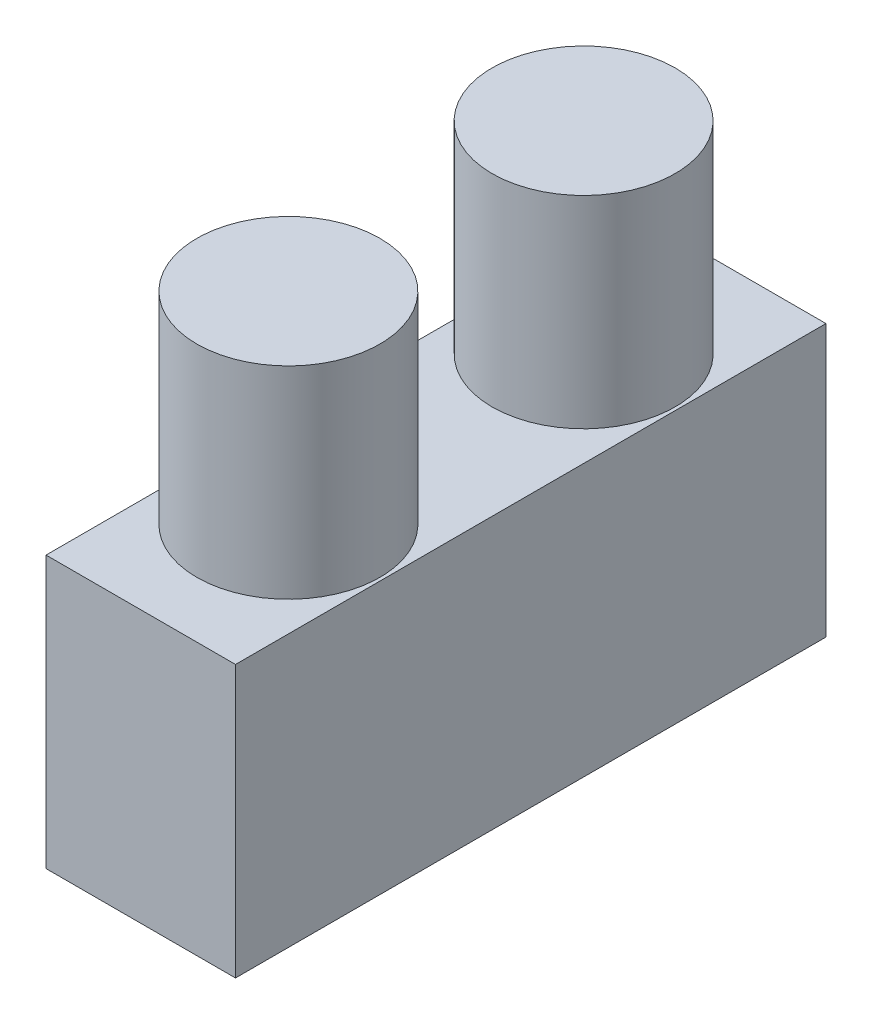
SolidWorks part; units mm, degrees
ref_plane "Front Plane" through (0, 0, 0) normal (0, 0, 1) x (1, 0, 0)
ref_plane "Top Plane" through (0, 0, 0) normal (0, 1, 0) x (1, 0, 0)
ref_plane "Right Plane" through (0, 0, 0) normal (1, 0, 0) x (0, 0, -1)
sketch "Sketch1" plane through (0, 0, 0) normal (0, 1, 0) x (1, 0, 0)
  line L1 (0, 0) -> (6, 0)
  line L2 (0, 0) -> (0, 18.7)
  line L3 (0, 18.7) -> (6, 18.7)
  line L4 (6, 0) -> (6, 18.7)
  dimension "D1" = 6
  dimension "D2" = 18.7
extrude "Boss-Extrude1" add sketch "Sketch1" along normal blind 8.6
sketch "Sketch2" plane through (0, 8.6, 0) normal (0, 1, 0) x (1, 0, 0)
  line L0 (3, 18.7) -> (3, 14.025) construction
  line L3 (6, 18.7) -> (0, 18.7) construction
  line L4 (3, 14.025) -> (3, 9.35) construction
  line L5 (3, 9.35) -> (3, 4.675) construction
  line L6 (3, 4.675) -> (3, 0) construction
  line L7 (0, 0) -> (6, 0) construction
  circle A0 centre (3, 14.025) radius 2.9
  circle A1 centre (3, 4.675) radius 2.9
  point P11 (0, 0)
  point P12 (0, 0)
  dimension "D2" = 5.8
extrude "Boss-Extrude2" add sketch "Sketch2" along normal blind 6.4
